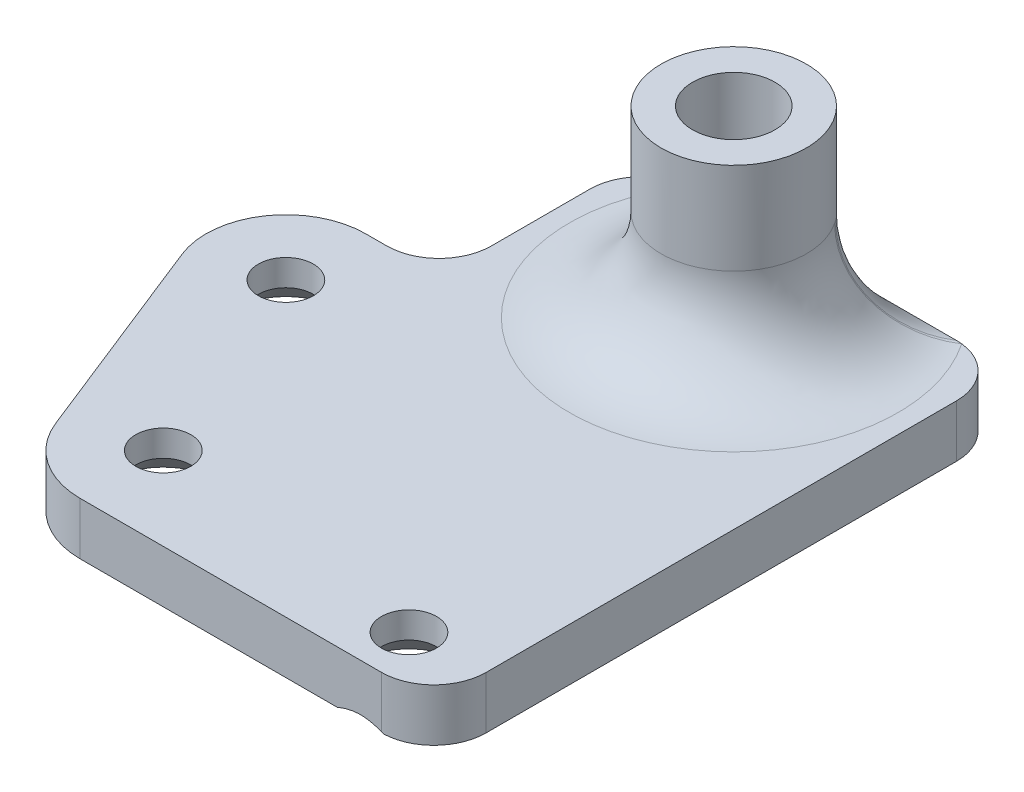
SolidWorks part; units mm, degrees
ref_plane "Front Plane" through (0, 0, 0) normal (0, 0, 1) x (1, 0, 0)
ref_plane "Top Plane" through (0, 0, 0) normal (0, 1, 0) x (1, 0, 0)
ref_plane "Right Plane" through (0, 0, 0) normal (1, 0, 0) x (0, 0, -1)
ref_axis "X-Axis" through (-88.4377, 0, 0) along (1, 0, 0)
ref_axis "Y-Axis" through (0, 0, -69.2525) along (0, 0, 1)
ref_axis "Z-Axis" through (0, -52.5493, 0) along (0, 1, 0)
sketch "Sketch1" plane through (0, 0, 0) normal (0, 1, 0) x (1, 0, 0)
  line L0 (0, 0) -> (-14, 0) construction
  line L4 (0, 0) -> (0, -9.3) construction
  line L5 (-16.8344, -1.1263) -> (-13.646, -9.1506)
  line L6 (-11.2, 10.8) -> (2.8, 10.8)
  line L7 (-11.2, 10.8) -> (-11.2, 3.05)
  line L9 (2.8, 10.8) -> (2.8, 3.8)
  line L11 (-14, 3.05) -> (-11.2, 3.05)
  line L12 (2.8, -11.15) -> (2.8, 3.8)
  line L14 (-11.2, 10.8) -> (2.8, 3.8) construction
  line L15 (-10.7, -11.15) -> (2.8, -11.15)
  circle A0 centre (-14, 0) radius 1.05
  circle A2 centre (0, -9.3) radius 1.05
  circle A3 centre (-10.7, -7.98) radius 1.05
  arc A4 (-14, 3.05) -> (-16.8344, -1.1263) centre (-14, 0) ccw
  circle A7 centre (-14, 0) radius 3.05 construction
  arc A8 (-13.646, -9.1506) -> (-10.7, -11.15) centre (-10.7, -7.98) ccw
  point P10 (-4.2, 7.3)
  point P14 (-4.2, 7.3)
  dimension "D5" = 2.1
  dimension "D9" = 9.8
  dimension "D1" = 14
  dimension "D2" = 9.3
  dimension "D3" = 10.7
  dimension "D4" = 1.32
  dimension "D6" = 14
  dimension "D7" = 3.5
  dimension "D10" = 16.6
  dimension "D11" = 1.85
  dimension "D8" = 2
extrude "Boss-Extrude1" add sketch "Sketch1" along normal blind 2
fillet "Fillet1" radius 2 4 edges at (2.8, 1, 11.15) (2.8, 1, -10.8) (-11.2, 1, -10.8) (-11.2, 1, -3.05)
sketch "Sketch2" plane through (0, 2, 0) normal (0, 1, 0) x (1, 0, 0)
  line L0 (-11.2, 10.8) -> (2.8, 3.8) construction
  circle A0 centre (-4.2, 7.3) radius 1.575
  circle A1 centre (-4.2, 7.3) radius 2.775
  dimension "D1" = 3.15
  dimension "D2" = 1.2
extrude "Boss-Extrude2" add sketch "Sketch2" along normal blind 7
fillet "Fillet2" radius 3.5 1 edges at (-4.2, 2, -4.525)
chamfer "Chamfer1" distance 1 angle 45 3 edges at (-10.7, 0, 9.03) (-14, 0, 1.05) (0, 0, 10.35)
